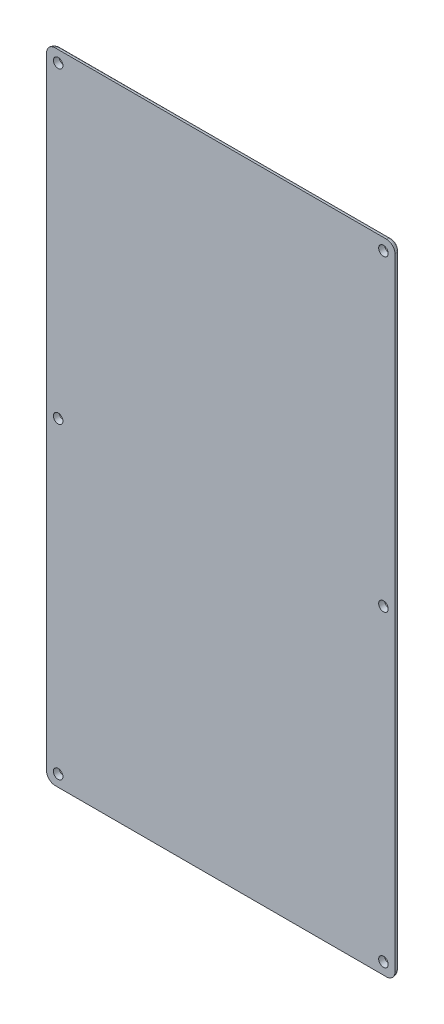
SolidWorks part; units mm, degrees
ref_plane "Front Plane" through (0, 0, 0) normal (0, 0, 1) x (1, 0, 0)
ref_plane "Top Plane" through (0, 0, 0) normal (0, 1, 0) x (1, 0, 0)
ref_plane "Right Plane" through (0, 0, 0) normal (1, 0, 0) x (0, 0, -1)
sketch "Sketch1" plane through (0, 0, 0) normal (0, 0, 1) x (1, 0, 0)
  line L1 (-60, -110) -> (60, -110)
  line L2 (-60, -110) -> (-60, 110)
  line L3 (-60, 110) -> (60, 110)
  line L4 (60, -110) -> (60, 110)
  line L5 (-60, -110) -> (60, 110) construction
  line L6 (-60, 110) -> (60, -110) construction
  point P1 (0, 0)
  dimension "D1" = 220
  dimension "D2" = 120
extrude "Boss-Extrude1" add sketch "Sketch1" along normal blind 2
sketch "Sketch3" plane through (0, 0, 2) normal (0, 0, 1) x (1, 0, 0)
  circle A0 centre (56, 106) radius 1.65
  circle A1 centre (-56, 106) radius 1.65
  circle A2 centre (-56, 0) radius 1.65
  circle A3 centre (-56, -106) radius 1.65
  circle A4 centre (56, -106) radius 1.65
  circle A5 centre (56, 0) radius 1.65
  dimension "D1" = 3.3
extrude "Cut-Extrude1" cut sketch "Sketch3" against normal through all
fillet "Fillet3" radius 3 4 edges at (60, 110, 1) (60, -110, 1) (-60, -110, 1) (-60, 110, 1)
fillet "Fillet1" radius 2 8 edges at (-60, 0, 0) (0, -110, 0) (60, 0, 0) (0, 110, 0) (59.1213, 109.1213, 0) (59.1213, -109.1213, 0) (-59.1213, -109.1213, 0) (-59.1213, 109.1213, 0)
equation "\"width\"= 31.00cm"
equation "\"length\"= 44.00cm"
equation "\"height\"= 49cm"
equation "\"top_height\"= 5cm"
equation "\"bot_height\"= 5cm"
equation "\"door_width\"= 5cm"
equation "\"thick\"= 0.2cm"
equation "\"left_length\"= 3cm"
equation "\"right_length\"= 3cm"
equation "\"pole_loc\"= 1cm"
equation "\"pole_dim\"= 1cm\"enc_length\" = 22cm"
